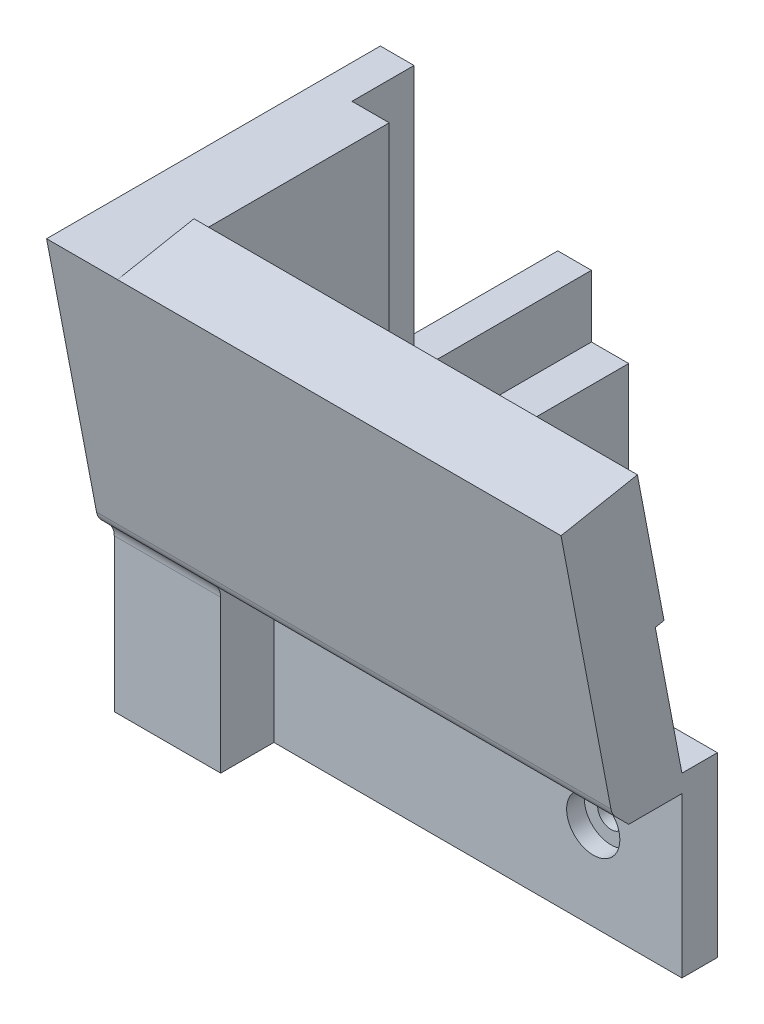
SolidWorks part; units mm, degrees
ref_plane "前视基准面" through (0, 0, 0) normal (0, 0, 1) x (1, 0, 0)
ref_plane "上视基准面" through (0, 0, 0) normal (0, 1, 0) x (1, 0, 0)
ref_plane "右视基准面" through (0, 0, 0) normal (1, 0, 0) x (0, 0, -1)
other "Configuration Table"
sketch "草图1" plane through (0, 0, 0) normal (1, 0, 0) x (0, 0, -1)
  line L0 (0, 0) -> (-10, 0)
  line L1 (-10, 0) -> (-17.6299, 40)
  line L2 (-17.6299, 40) -> (-10, 41.4554)
  line L3 (-10, 41.4554) -> (-4, 10)
  line L4 (-4, 10) -> (0, 10)
  line L5 (0, 10) -> (0, 0)
  dimension "D1" = 10
  dimension "D2" = 4
  dimension "D3" = 10
  dimension "D4" = 6
  dimension "D5" = 40
extrude "凸台-拉伸1" add sketch "草图1" along normal blind 50
sketch "草图2" plane through (0, 0, 0) normal (0, -1, 0) x (1, 0, 0)
  line L4 (0, 10) -> (0, 0)
  line L5 (0, 0) -> (50, 0)
  line L6 (50, 0) -> (50, 10)
  line L7 (50, 10) -> (0, 10)
  line L8 (0, 10) -> (0, 0)
  line L9 (0, 0) -> (50, 0)
  line L10 (50, 0) -> (50, 10)
  line L11 (50, 10) -> (0, 10)
  dimension "D1" = 0
extrude "凸台-拉伸2" add sketch "草图2" along normal blind 10
sketch "草图3" plane through (0, 0, 0) normal (-1, 0, 0) x (0, 0, 1)
  line L1 (0, 10) -> (10, 10)
  line L2 (0, 10) -> (0, -10)
  line L3 (0, -10) -> (10, -10)
  line L4 (10, 10) -> (10, -10)
extrude "凸台-拉伸3" add sketch "草图3" along normal blind 20
sketch "草图4" plane through (0, 10, 0) normal (0, 1, 0) x (1, 0, 0)
  line L1 (-20, 0) -> (0, 0)
  line L2 (-20, 0) -> (-20, -10)
  line L3 (-20, -10) -> (0, -10)
  line L4 (0, 0) -> (0, -10)
extrude "凸台-拉伸4" add sketch "草图4" along normal blind 30
sketch "草图5" plane through (50, 0, 0) normal (1, 0, 0) x (0, 0, -1)
  line L0 (-10, 10.004) -> (-11.9082, 10.004)
  line L1 (-17.6299, 40) -> (-10, 0) construction
  line L2 (-11.9082, 10.004) -> (-10, 0)
  line L3 (-10, 0) -> (-10, 10.004)
extrude "切除-拉伸1" cut sketch "草图5" against normal up to surface (50 mm away) up to face at (0, 32.2911, 11.4705)
chamfer "倒角1" distance 2 angle 45 1 edges at (25, 10.004, 10)
sketch "草图9" plane through (0, 0, 10) normal (0, 0, 1) x (1, 0, 0)
  line L0 (-20, 40) -> (-10, 40) construction
  line L1 (-20, 40) -> (0, 40) construction
  line L2 (-10, 40) -> (-10, 20) construction
  line L3 (50, -10) -> (50, 0) construction
  line L4 (50, -10) -> (50, 8.004) construction
  line L5 (50, 0) -> (40, 0) construction
  circle A0 centre (-10, 20) radius 1.5
  circle A1 centre (40, 0) radius 1.5
  dimension "D3" = 3
  dimension "D5" = 3
  dimension "D1" = 10
  dimension "D2" = 20
  dimension "D4" = 10
extrude "切除-拉伸2" cut sketch "草图9" against normal through all
sketch "草图12" plane through (0, 0, 10) normal (0, 0, 1) x (1, 0, 0)
  line L8 (0, 40) -> (-20, 40)
  line L9 (50, -10) -> (50, 8.004)
  line L10 (50, 8.004) -> (0, 8.004)
  line L11 (0, 8.004) -> (0, 40)
  line L15 (50, -10) -> (50, 8.004)
  line L16 (50, 8.004) -> (0, 8.004)
  line L17 (0, 8.004) -> (0, 40)
  line L19 (0, 40) -> (-20, 40)
  line L20 (-20, 40) -> (-20, -10)
  line L21 (-20, 40) -> (-20, -10)
  line L22 (-20, -10) -> (50, -10)
  line L23 (-20, -10) -> (50, -10)
  dimension "D1" = 0
extrude "切除-拉伸4" cut sketch "草图12" against normal blind 6
sketch "草图13" plane through (0, 8.004, 0) normal (0, -1, 0) x (1, 0, 0)
  line L0 (50, 4) -> (0, 4) construction
  line L1 (0, 10) -> (4, 10)
  line L2 (0, 10) -> (0, 4)
  line L3 (0, 4) -> (4, 4)
  line L4 (4, 10) -> (4, 4)
  line L6 (50, 10) -> (46, 10)
  line L7 (50, 10) -> (50, 4)
  line L8 (50, 4) -> (46, 4)
  line L9 (46, 10) -> (46, 4)
  dimension "D1" = 4
  dimension "D2" = 4
extrude "凸台-拉伸12" add sketch "草图13" along normal up to surface (18.004 mm away) up to face at (15, -10, 2)
fillet "圆角2" radius 2 3 edges at (25, 9.8906, 11.8866) (48, 8.004, 10) (2, 8.004, 10)
sketch "草图14" plane through (0, 0, 4) normal (0, 0, 1) x (1, 0, 0)
  line L0 (-20, -10) -> (0, -10) construction
  line L1 (-20, 40) -> (-4, 40)
  line L2 (-20, 40) -> (-20, -10)
  line L3 (-20, -10) -> (-4, -10)
  line L4 (-4, 40) -> (-4, -10)
  dimension "D1" = 16
extrude "切除-拉伸5" cut sketch "草图14" against normal blind 10
sketch "草图16" plane through (0, 0, 0) normal (1, 0, 0) x (0, 0, -1)
  line L0 (0, 10) -> (-4, 10)
  line L1 (-4, 10) -> (-5.9075, 20)
  line L2 (-4, 10) -> (-10, 41.4554) construction
  line L3 (-5.9075, 20) -> (0, 20)
  line L4 (0, 40) -> (0, 10) construction
  line L5 (0, 20) -> (0, 10)
  dimension "D1" = 10
extrude "凸台-拉伸14" add sketch "草图16" along normal blind 10
sketch "草图17" plane through (0, 0, 0) normal (0, 0, -1) x (-1, 0, 0)
  line L1 (0, 40) -> (4, 40)
  line L2 (0, 40) -> (0, -10)
  line L3 (0, -10) -> (4, -10)
  line L4 (4, 40) -> (4, -10)
extrude "凸台-拉伸15" add sketch "草图17" along normal blind 20
sketch "草图20" plane through (-4, 0, 0) normal (-1, 0, 0) x (0, 0, 1)
  line L0 (4, 20) -> (5.9075, 20) construction
  line L1 (4, 12) -> (-20, 12)
  line L2 (4, 12) -> (4, -10)
  line L3 (4, -10) -> (-20, -10)
  line L4 (-20, 12) -> (-20, -10)
  dimension "D1" = 8
extrude "切除-拉伸8" cut sketch "草图20" against normal up to surface (4 mm away) up to face at (0, 13.7188, 9.5514)
sketch "草图21" plane through (0, 0, 4) normal (0, 0, 1) x (1, 0, 0)
  line L5 (-4, 12) -> (0, 12)
  line L6 (0, 12) -> (0, 20)
  line L7 (0, 20) -> (0, 40)
  line L8 (0, 40) -> (-4, 40)
  line L9 (-4, 40) -> (-4, 12)
  line L10 (-4, 12) -> (0, 12)
  line L11 (0, 12) -> (0, 20)
  line L12 (0, 20) -> (0, 40)
  line L13 (0, 40) -> (-4, 40)
  line L14 (-4, 40) -> (-4, 12)
  dimension "D1" = 0
extrude "凸台-拉伸16" add sketch "草图21" along normal up to surface (13.6299 mm away) up to face at (25, 25.2475, 14.8159)
sketch "草图22" plane through (0, 12, 0) normal (0, -1, 0) x (1, 0, 0)
  line L1 (0, 0) -> (-4, 0)
  line L2 (0, 0) -> (0, 12.289)
  line L3 (0, 12.289) -> (-4, 12.289)
  line L4 (-4, 0) -> (-4, 12.289)
extrude "凸台-拉伸17" add sketch "草图22" along normal up to surface (22 mm away) up to face at (25, -10, 6)
sketch "草图23" plane through (0, 0, 0) normal (1, 0, 0) x (0, 0, -1)
  line L5 (-12.0019, 10.495) -> (-12.289, 12)
  line L6 (-12.289, 12) -> (-12.289, -10)
  line L7 (-12.289, -10) -> (-10, -10)
  line L8 (-10, -10) -> (-10, 7.1755)
  line L9 (-10.5858, 8.5898) -> (-11.4515, 9.4555)
  line L10 (-12.0019, 10.495) -> (-12.289, 12)
  line L11 (-12.289, 12) -> (-12.289, -10)
  line L12 (-12.289, -10) -> (-10, -10)
  line L13 (-10, -10) -> (-10, 7.1755)
  line L14 (-10.5858, 8.5898) -> (-11.4515, 9.4555)
  arc A2 (-12.0019, 10.495) -> (-11.4515, 9.4555) centre (-10.0373, 10.8697) ccw
  arc A3 (-10, 7.1755) -> (-10.5858, 8.5898) centre (-12, 7.1755) ccw
  arc A4 (-12.0019, 10.495) -> (-11.4515, 9.4555) centre (-10.0373, 10.8697) ccw
  arc A5 (-10, 7.1755) -> (-10.5858, 8.5898) centre (-12, 7.1755) ccw
  dimension "D1" = 0
extrude "切除-拉伸9" cut sketch "草图23" against normal up to surface (4 mm away) up to face at (-4, 13.7143, 0.3154)
sketch "草图24" plane through (46, 0, 0) normal (-1, 0, 0) x (0, 0, 1)
  line L5 (4, -10) -> (10, -10)
  line L6 (10, -10) -> (10, 7.1755)
  line L7 (10.5858, 8.5898) -> (10, 8.004)
  line L8 (10, 8.004) -> (4, 8.004)
  line L9 (4, 8.004) -> (4, -10)
  line L10 (4, -10) -> (10, -10)
  line L11 (10, -10) -> (10, 7.1755)
  line L12 (10.5858, 8.5898) -> (10, 8.004)
  line L13 (10, 8.004) -> (4, 8.004)
  line L14 (4, 8.004) -> (4, -10)
  arc A1 (10.5858, 8.5898) -> (10, 7.1755) centre (12, 7.1755) ccw
  arc A2 (10.5858, 8.5898) -> (10, 7.1755) centre (12, 7.1755) ccw
  dimension "D1" = 0
extrude "切除-拉伸10" cut sketch "草图24" against normal up to surface (4 mm away) up to face at (50, 11.7188, 8.5607)
sketch "草图25" plane through (0, 0, 4) normal (0, 0, 1) x (1, 0, 0)
  circle A0 centre (40, 0) radius 3
  dimension "D1" = 6
extrude "切除-拉伸11" cut sketch "草图25" against normal offset from surface (2 mm away) 2 up to face at (41.5, 0, 0)
sketch "草图26" plane through (10, 0, 0) normal (1, 0, 0) x (0, 0, -1)
  line L4 (0, 10) -> (0, 20)
  line L5 (0, 20) -> (-5.9075, 20)
  line L6 (-5.9075, 20) -> (-4, 10)
  line L7 (-4, 10) -> (0, 10)
  line L8 (0, 10) -> (0, 20)
  line L9 (0, 20) -> (-5.9075, 20)
  line L10 (-5.9075, 20) -> (-4, 10)
  line L11 (-4, 10) -> (0, 10)
  dimension "D1" = 0
extrude "切除-拉伸12" cut sketch "草图26" against normal blind 10
sketch "草图27" plane through (-4, 0, 0) normal (-1, 0, 0) x (0, 0, 1)
  line L0 (-20, 40) -> (-20, 12)
  line L1 (-20, 12) -> (-20, 40) construction
  line L8 (0, -10) -> (10, -10)
  line L9 (10, -10) -> (10, 7.1755)
  line L10 (10.5858, 8.5898) -> (11.4515, 9.4555)
  line L11 (12.0019, 10.495) -> (17.6299, 40)
  line L12 (17.6299, 40) -> (-20, 40)
  line L13 (-20, 40) -> (-20, 12)
  line L14 (-20, 12) -> (0, 12)
  line L15 (0, 12) -> (0, -10)
  line L16 (0, -10) -> (10, -10)
  line L17 (10, -10) -> (10, 7.1755)
  line L18 (10.5858, 8.5898) -> (11.4515, 9.4555)
  line L19 (12.0019, 10.495) -> (17.6299, 40)
  line L20 (17.6299, 40) -> (-20, 40)
  line L22 (-20, 12) -> (0, 12)
  line L23 (0, 12) -> (0, -10)
  arc A2 (10.5858, 8.5898) -> (10, 7.1755) centre (12, 7.1755) ccw
  arc A3 (11.4515, 9.4555) -> (12.0019, 10.495) centre (10.0373, 10.8697) ccw
  arc A4 (10.5858, 8.5898) -> (10, 7.1755) centre (12, 7.1755) ccw
  arc A5 (11.4515, 9.4555) -> (12.0019, 10.495) centre (10.0373, 10.8697) ccw
  dimension "D2" = 0
  dimension "D1" = 0
extrude "凸台-拉伸19" add sketch "草图27" along normal blind 4
sketch "草图34" plane through (0, 12, 0) normal (0, -1, 0) x (1, 0, 0)
  line L4 (0, 0) -> (-8, 0)
  line L5 (-8, 0) -> (-8, -20)
  line L6 (-8, -20) -> (0, -20)
  line L7 (0, -20) -> (0, 0)
  line L8 (0, 0) -> (-8, 0)
  line L9 (-8, 0) -> (-8, -20)
  line L10 (-8, -20) -> (0, -20)
  line L11 (0, -20) -> (0, 0)
  dimension "D1" = 0
extrude "凸台-拉伸21" add sketch "草图34" along normal up to surface (22 mm away) up to face at (15.3333, -10, 4.6667)
sketch "草图35" plane through (0, 0, -20) normal (0, 0, -1) x (-1, 0, 0)
  line L0 (0, -10) -> (0, 10) construction
  line L1 (8, -10) -> (0, -10)
  line L2 (8, -10) -> (8, 10)
  line L3 (8, 10) -> (0, 10)
  line L4 (0, -10) -> (0, 10)
  dimension "D1" = 20
extrude "凸台-拉伸22" add sketch "草图35" along normal blind 20
sketch "草图28" plane through (0, 0, 0) normal (1, 0, 0) x (0, 0, -1)
  line L1 (20, 40) -> (13, 40)
  line L2 (20, 40) -> (20, 10)
  line L3 (20, 3) -> (13, 3)
  line L4 (13, 40) -> (13, 3)
  line L5 (40, 10) -> (20, 10) construction
  line L6 (40, 10) -> (40, -10) construction
  line L7 (20, 3) -> (40, 3)
  line L9 (20, 10) -> (40, 10)
  line L10 (40, 3) -> (40, 10)
  dimension "D1" = 7
  dimension "D2" = 7
extrude "切除-拉伸18" cut sketch "草图28" against normal blind 4.2
sketch "草图38" plane through (-8, 0, 0) normal (-1, 0, 0) x (0, 0, 1)
  line L0 (-40, 0) -> (-30, 0) construction
  line L1 (-40, -10) -> (-40, 10) construction
  circle A0 centre (-30, 0) radius 1.5
  dimension "D2" = 3
  dimension "D1" = 10
extrude "切除-拉伸19" cut sketch "草图38" against normal through all
sketch "草图39" plane through (-8, 0, 0) normal (-1, 0, 0) x (0, 0, 1)
  circle A0 centre (-30, 0) radius 2.9
  dimension "D1" = 5.8
extrude "切除-拉伸20" cut sketch "草图39" against normal offset from surface (6 mm away) 2 up to face at (0, 0, -28.5)
sketch "草图42" plane through (0, -0.3851, 2.0191) normal (0, 0.1874, -0.9823) x (-1, 0, 0)
  line L0 (-50, 10.5724) -> (-50, 42.5949) construction
  line L1 (-50, 26.5836) -> (0, 26.5836)
  line L2 (-50, 26.5836) -> (-50, 42.5949)
  line L3 (-50, 42.5949) -> (0, 42.5949)
  line L4 (0, 26.5836) -> (0, 42.5949)
extrude "凸台-拉伸23" add sketch "草图42" along normal blind 1
